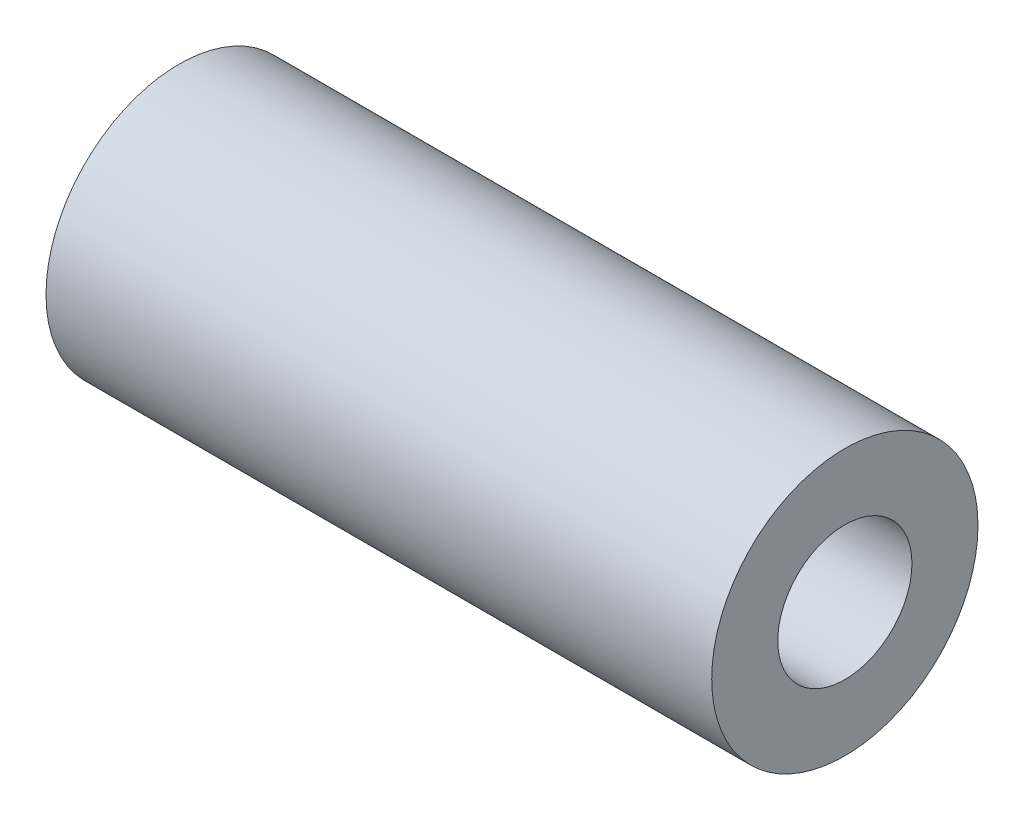
SolidWorks part; units mm, degrees
material "Nylon 101"
ref_plane "Front Plane" through (0, 0, 0) normal (0, 0, 1) x (1, 0, 0)
ref_plane "Top Plane" through (0, 0, 0) normal (0, 1, 0) x (1, 0, 0)
ref_plane "Right Plane" through (0, 0, 0) normal (1, 0, 0) x (0, 0, -1)
sketch "Sketch1" plane through (0, 0, 0) normal (1, 0, 0) x (0, 0, -1)
  circle A0 centre (0, 0) radius 3.2004
  circle A1 centre (0, 0) radius 6.35
  dimension "D1" = 12.7
  dimension "D2" = 6.4008
extrude "Boss-Extrude1" add sketch "Sketch1" along normal blind 31.75
